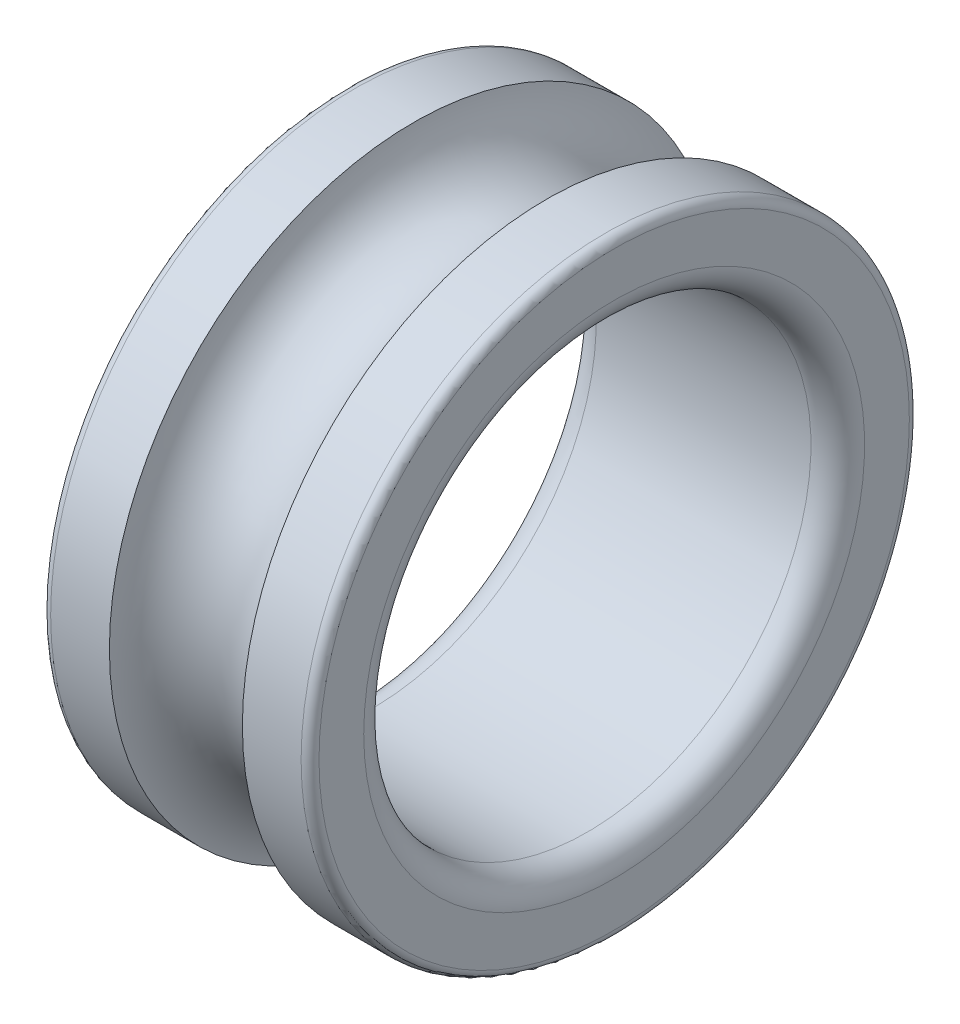
SolidWorks part; units mm, degrees
ref_plane "Front Plane" through (0, 0, 0) normal (0, 0, 1) x (1, 0, 0)
ref_plane "Top Plane" through (0, 0, 0) normal (0, 1, 0) x (1, 0, 0)
ref_plane "Right Plane" through (0, 0, 0) normal (1, 0, 0) x (0, 0, -1)
ref_plane "Plane1" through (0, 0, 0) normal (0, 0, -1) x (-1, 0, 0)
sketch "Sketch1" plane through (0, 0, 0) normal (0, 0, -1) x (-1, 0, 0)
  line L0 (-2.35, 3.4) -> (-3.0067, 3.4)
  line L1 (-4.4933, 3.4) -> (-5.15, 3.4)
  line L2 (-5.25, 3.3) -> (-5.25, 2.8)
  line L3 (-4.95, 2.5) -> (-2.55, 2.5)
  line L4 (-2.25, 2.8) -> (-2.25, 3.3)
  line L5 (-7.0013, 0) -> (0.0013, 0) construction
  line L6 (-15.6375, 0) -> (14.6064, 0) construction
  line L7 (-3.75, 3.5) -> (-3.75, -5.115) construction
  arc A0 (-3.0067, 3.4) -> (-4.4933, 3.4) centre (-3.75, 3.5) cw
  arc A1 (-5.15, 3.4) -> (-5.25, 3.3) centre (-5.15, 3.3) ccw
  arc A2 (-5.25, 2.8) -> (-4.95, 2.5) centre (-4.95, 2.8) ccw
  arc A3 (-2.55, 2.5) -> (-2.25, 2.8) centre (-2.55, 2.8) ccw
  arc A4 (-2.25, 3.3) -> (-2.35, 3.4) centre (-2.35, 3.3) ccw
  dimension "D2" = 0.3
  dimension "D3" = 0.75
  dimension "D1" = 5
  dimension "D4" = 6.8
  dimension "D5" = 7
  dimension "D6" = 3
revolve "Revolve1" add sketch "Sketch1" angle 360 about L5 reverse direction yes
